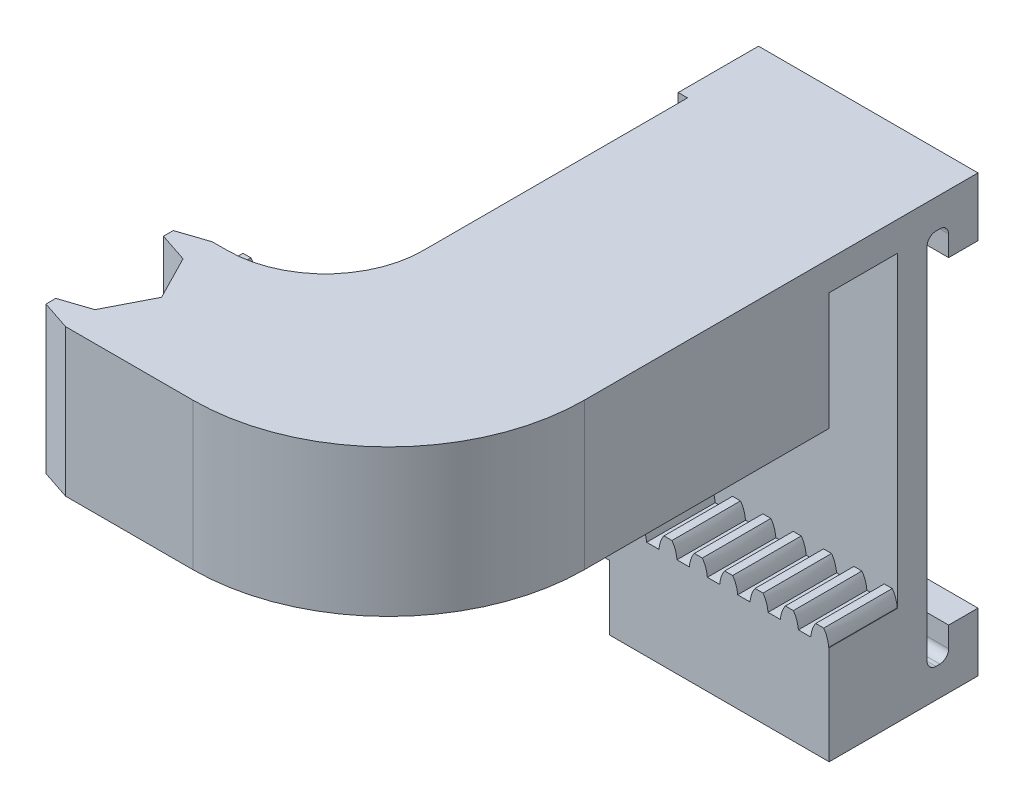
SolidWorks part; units mm, degrees
ref_plane "Vorne" through (0, 0, 0) normal (0, 0, 1) x (1, 0, 0)
ref_plane "Oben" through (0, 0, 0) normal (0, 1, 0) x (1, 0, 0)
ref_plane "Rechts" through (0, 0, 0) normal (1, 0, 0) x (0, 0, -1)
sketch "Skizze1" plane through (0, 0, 0) normal (0, 1, 0) x (1, 0, 0)
  line L0 (30.6932, 31.8315) -> (30.6932, -23.1685)
  line L3 (9.2244, 31.8315) -> (30.6932, 31.8315)
  line L5 (30.6932, -23.1685) -> (-2.3068, -23.1685)
  line L7 (9.2244, 31.8315) -> (9.2244, -8.1685)
  line L8 (9.2244, -8.1685) -> (-2.3068, -8.1685)
  line L9 (-2.3068, -8.1685) -> (-5.3068, -9.1685)
  line L10 (-5.3068, -9.1685) -> (-5.3068, -10.1685)
  line L11 (-5.3068, -10.1685) -> (-2.3068, -11.1685)
  line L12 (-5.3068, -13.1685) -> (-2.3068, -14.1685)
  line L13 (-5.3068, -12.1685) -> (-5.3068, -13.1685)
  line L14 (-2.3068, -11.1685) -> (-5.3068, -12.1685)
  line L15 (-5.3068, -16.1685) -> (-2.3068, -17.1685)
  line L16 (-5.3068, -15.1685) -> (-5.3068, -16.1685)
  line L17 (-2.3068, -14.1685) -> (-5.3068, -15.1685)
  line L18 (-5.3068, -19.1685) -> (-2.3068, -20.1685)
  line L19 (-5.3068, -18.1685) -> (-5.3068, -19.1685)
  line L20 (-2.3068, -17.1685) -> (-5.3068, -18.1685)
  line L21 (-5.3068, -22.1685) -> (-2.3068, -23.1685)
  line L22 (-5.3068, -21.1685) -> (-5.3068, -22.1685)
  line L23 (-2.3068, -20.1685) -> (-5.3068, -21.1685)
  point P0 (-5.3068, -8.1685)
  dimension "D2" = 3
  dimension "D1" = 55
  dimension "D3" = 21.4688
  dimension "D4" = 33
  dimension "D5" = 15
  dimension "D6" = 1
  dimension "D7" = 0
  dimension "D8" = 1
  dimension "D9" = 1
  dimension "D10" = 5
extrude "Aufsatz-Linear austragen1" add sketch "Skizze1" along normal blind 3 contours L3 region at (17.3865, 0, -1.3979)
sketch "Skizze2" plane through (0, 0, -31.8315) normal (0, 0, -1) x (-1, 0, 0)
  line L3 (-30.6932, 3) -> (-8.273, 3)
  line L7 (-30.6932, -41.5) -> (-8.273, -41.5)
  line L9 (-9.2244, 3) -> (-30.6932, 3) construction
  line L10 (-30.6932, 3) -> (-30.6932, -41.5)
  line L11 (-8.273, -41.5) -> (-8.273, 3)
  line L13 (-30.6932, 3) -> (-30.6932, 0) construction
  dimension "D1" = 44.5
  dimension "D2" = 0
  dimension "D3" = 22.4202
  dimension "D4" = 0
extrude "Aufsatz-Linear austragen2" add sketch "Skizze2" against normal blind 3
sketch "Skizze3" plane through (30.6932, 0, 0) normal (1, 0, 0) x (0, 0, -1)
  line L4 (37.0315, 3) -> (37.0315, 0)
  line L6 (37.0315, 0) -> (37.0315, -3)
  line L7 (37.0315, -3) -> (34.0315, -3)
  line L8 (34.0315, -0.9) -> (34.0315, -3)
  line L9 (28.8315, -41.5) -> (37.0315, -41.5)
  line L12 (37.0315, -41.5) -> (37.0315, -38.5)
  line L14 (37.0315, -38.5) -> (37.0315, -35.5)
  line L15 (37.0315, -35.5) -> (34.0315, -35.5)
  line L16 (34.0315, -37.6) -> (34.0315, -35.5)
  line L21 (31.8315, -3) -> (31.8315, -0.9)
  line L22 (31.8315, -3) -> (28.8315, -3)
  line L25 (32.7315, -38.5) -> (33.1315, -38.5)
  line L26 (32.7315, 0) -> (33.1315, 0)
  line L27 (37.0315, 3) -> (28.8315, 3)
  line L28 (28.8315, 3) -> (28.8315, -3)
  line L30 (31.8315, -37.6) -> (31.8315, -35.5)
  line L31 (31.8315, -35.5) -> (28.8315, -35.5)
  line L32 (28.8315, -35.5) -> (28.8315, -41.5)
  line L35 (31.8315, 3) -> (-23.1685, 3) construction
  arc A4 (34.0315, -0.9) -> (33.1315, 0) centre (33.1315, -0.9) ccw
  arc A5 (31.8315, -0.9) -> (32.7315, 0) centre (32.7315, -0.9) cw
  arc A6 (34.0315, -37.6) -> (33.1315, -38.5) centre (33.1315, -37.6) cw
  arc A7 (31.8315, -37.6) -> (32.7315, -38.5) centre (32.7315, -37.6) ccw
  dimension "D9" = 3
  dimension "D11" = 0.9
  dimension "D16" = 0.4
  dimension "D1" = 3
  dimension "D2" = 6
  dimension "D3" = 3
  dimension "D4" = 3
  dimension "D5" = 3
  dimension "D6" = 8.2
  dimension "D7" = 3
  dimension "D8" = 3
  dimension "D10" = 3
  dimension "D12" = 6
  dimension "D13" = 8.2
  dimension "D14" = 3
  dimension "D15" = 44.5
  dimension "D17" = 6
  dimension "D18" = 3
extrude "Aufsatz-Linear austragen3" add sketch "Skizze3" against normal up to surface (22.4202 mm away) contours L28 L22 L21 A5 L26 A4 L8 L7 L6 L4 L27 | L30 L31 L32 L9 L12 L14 L15 L16 A6 L25 A7 up to face at (8.273, -19.25, -30.3315)
sketch "Skizze4" plane through (0, 0, -28.8315) normal (0, 0, 1) x (1, 0, 0)
  line L0 (30.6932, 0) -> (30.6932, -41.5) construction
  line L5 (9.2206, -31.4) -> (-34.71, -31.4)
  line L7 (9.2206, -34.9) -> (-34.71, -34.9)
  line L8 (-34.71, -31.4) -> (-34.71, -34.9)
  line L13 (30.6932, -41.5) -> (8.273, -41.5) construction
  line L14 (9.2206, -31.4) -> (11.7031, -31.4)
  line L16 (9.2206, -34.9) -> (11.7031, -34.9)
  line L18 (11.7031, -34.9) -> (30.6932, -34.9)
  line L20 (11.7031, -31.4) -> (30.6932, -31.4)
  line L21 (30.6932, -34.9) -> (30.6932, -31.4)
  dimension "D1" = 3.5
  dimension "D2" = 10.1
extrude "Aufsatz-Linear austragen4" add sketch "Skizze4" along normal blind 7
sketch "Skizze5" plane through (0, 0, -21.8315) normal (0, 0, 1) x (1, 0, 0)
  line L0 (8.9471, -31.4) -> (7.1052, -31.4)
  line L1 (7.6184, -29.9477) -> (8.4339, -29.9477)
  line L27 (30.6932, -31.4) -> (-34.71, -31.4) construction
  spline S0 degree 2 poles (7.6184, -29.9477) (7.2013, -30.5085) (7.1052, -31.4) knots 0 0 0 1 1 1
  spline S1 degree 2 poles (8.4339, -29.9477) (8.8511, -30.5085) (8.9471, -31.4) knots 0 0 0 1 1 1
  point P4 (8.0262, 3)
  point P5 (8.0262, 4.4523)
  dimension "D1" = 0
  dimension "D2" = 1.4523
extrude "Aufsatz-Linear austragen5" add sketch "Skizze5" against normal blind 7 contours L0 S0 L1 S1
pattern_linear "Lineares Muster1" count 14 spacing 3.1 along (-1, 0, 0) count 8 spacing 3.1 along (1, 0, 0) of "Aufsatz-Linear austragen5"
sketch "Skizze6" plane through (0, 0, -21.8315) normal (0, 0, 1) x (1, 0, 0)
  line L0 (30.6932, -34.9) -> (30.6932, -41.5) construction
  line L1 (8.273, -34.9) -> (30.6932, -34.9)
  line L2 (8.273, -34.9) -> (8.273, -41.5)
  line L3 (8.273, -41.5) -> (30.6932, -41.5)
  line L4 (30.6932, -34.9) -> (30.6932, -41.5)
  line L5 (30.6932, -41.5) -> (8.273, -41.5) construction
  dimension "D1" = 0
  dimension "D2" = 0
extrude "Aufsatz-Linear austragen6" add sketch "Skizze6" against normal up to surface (7 mm away) up to face at (19.04, -26.7964, -28.8315)
fillet "Verrundung1" radius 20 1 edges at (30.6932, 1.5, 23.1685)
fillet "Verrundung2" radius 10 1 edges at (9.2244, 1.5, 8.1685)
sketch "Skizze7" plane through (-34.71, 0, 0) normal (-1, 0, 0) x (0, 0, 1)
  line L0 (-28.8315, -29.9477) -> (-21.8315, -29.9477) construction
  line L1 (-28.8315, -34.9) -> (-25.3315, -34.9)
  line L2 (-28.8315, -34.9) -> (-28.8315, -29.9477)
  line L3 (-28.8315, -29.9477) -> (-25.3315, -29.9477)
  line L4 (-25.3315, -34.9) -> (-25.3315, -29.9477)
extrude "Schnitt-Linear austragen1" cut sketch "Skizze7" against normal up to surface (42.983 mm away) up to face at (8.273, -21.4604, -32.0947)
sketch "Skizze9" plane through (0, 0, 0) normal (0, -1, 0) x (1, 0, 0)
  line L0 (9.2244, -1.8315) -> (9.2244, -21.8315)
  line L1 (8.273, -21.8315) -> (30.6932, -21.8315) construction
  line L2 (9.2244, -28.8315) -> (9.2244, -1.8315) construction
  line L3 (9.2244, -21.8315) -> (30.6932, -21.8315)
  line L4 (30.6932, -21.8315) -> (30.6932, 3.1685)
  line L5 (10.6932, 23.1685) -> (-2.3068, 23.1685)
  line L6 (-2.3068, 23.1685) -> (-5.3068, 22.1685)
  line L7 (-5.3068, 22.1685) -> (-5.3068, 21.1685)
  line L8 (-5.3068, 21.1685) -> (-2.3068, 20.1685)
  line L9 (-2.3068, 20.1685) -> (-5.3068, 19.1685)
  line L10 (-5.3068, 19.1685) -> (-5.3068, 18.1685)
  line L11 (-5.3068, 18.1685) -> (-2.3068, 17.1685)
  line L12 (-5.3068, 16.1685) -> (-2.3068, 17.1685) construction
  line L13 (-2.3068, 17.1685) -> (-5.3068, 18.1685) construction
  line L14 (-2.3068, 17.1685) -> (-5.3068, 16.1685)
  line L15 (-5.3068, 16.1685) -> (-5.3068, 15.1685)
  line L16 (-5.3068, 15.1685) -> (-2.3068, 14.1685)
  line L17 (-2.3068, 14.1685) -> (-5.3068, 13.1685)
  line L18 (-5.3068, 13.1685) -> (-5.3068, 12.1685)
  line L19 (-5.3068, 12.1685) -> (-2.3068, 11.1685)
  line L20 (-2.3068, 11.1685) -> (-5.3068, 10.1685)
  line L21 (-5.3068, 10.1685) -> (-5.3068, 9.1685)
  line L22 (-5.3068, 9.1685) -> (-2.3068, 8.1685)
  line L23 (-2.3068, 8.1685) -> (-0.7756, 8.1685)
  arc A1 (9.2244, -1.8315) -> (-0.7756, 8.1685) centre (-0.7756, -1.8315) ccw
  arc A2 (30.6932, 3.1685) -> (10.6932, 23.1685) centre (10.6932, 3.1685) ccw
  line M23 (30.6932, -28.8315) -> (30.6932, 3.1685)
  arc M24 (30.6932, 3.1685) -> (10.6932, 23.1685) centre (10.6932, 3.1685) ccw
  line M25 (10.6932, 23.1685) -> (-2.3068, 23.1685)
  line M26 (-2.3068, 23.1685) -> (-5.3068, 22.1685)
  line M27 (-5.3068, 22.1685) -> (-5.3068, 21.1685)
  line M28 (-5.3068, 21.1685) -> (-2.3068, 20.1685)
  line M29 (-2.3068, 20.1685) -> (-5.3068, 19.1685)
  line M30 (-5.3068, 19.1685) -> (-5.3068, 18.1685)
  line M31 (-5.3068, 18.1685) -> (-2.3068, 17.1685)
  line M32 (-2.3068, 17.1685) -> (-5.3068, 16.1685)
  line M34 (-5.3068, 15.1685) -> (-2.3068, 14.1685)
  line M35 (-2.3068, 14.1685) -> (-5.3068, 13.1685)
  line M36 (-5.3068, 13.1685) -> (-5.3068, 12.1685)
  line M37 (-5.3068, 12.1685) -> (-2.3068, 11.1685)
  line M38 (-2.3068, 11.1685) -> (-5.3068, 10.1685)
  line M39 (-5.3068, 10.1685) -> (-5.3068, 9.1685)
  line M40 (-5.3068, 9.1685) -> (-2.3068, 8.1685)
  line M41 (-2.3068, 8.1685) -> (-0.7756, 8.1685)
  arc M42 (-0.7756, 8.1685) -> (9.2244, -1.8315) centre (-0.7756, -1.8315) cw
  line M43 (9.2244, -1.8315) -> (9.2244, -28.8315)
extrude "Aufsatz-Linear austragen7" add sketch "Skizze9" along normal blind 12 contours L3 L11 M32 M34 M35 M36 M37 M38 M39 M40 M41 M42 M43 M23 M24 M25 M26 M27 M28 M29 M30 M31 region at (15.9978, 0, 2.1256)
sketch "Skizze10" plane through (0, -12, 0) normal (0, -1, 0) x (1, 0, 0)
  line L0 (-2.3068, 20.1685) -> (0, 15.6685)
  line L1 (0, 15.6685) -> (-2.3068, 11.1685)
  line L2 (-2.3068, 11.1685) -> (-7.7712, 11.1685)
  line L3 (-7.7712, 11.1685) -> (-7.7712, 20.2039)
  line L4 (-7.7712, 20.2039) -> (-2.3068, 20.1685)
extrude "Schnitt-Linear austragen2" cut sketch "Skizze10" against normal blind 22.95
